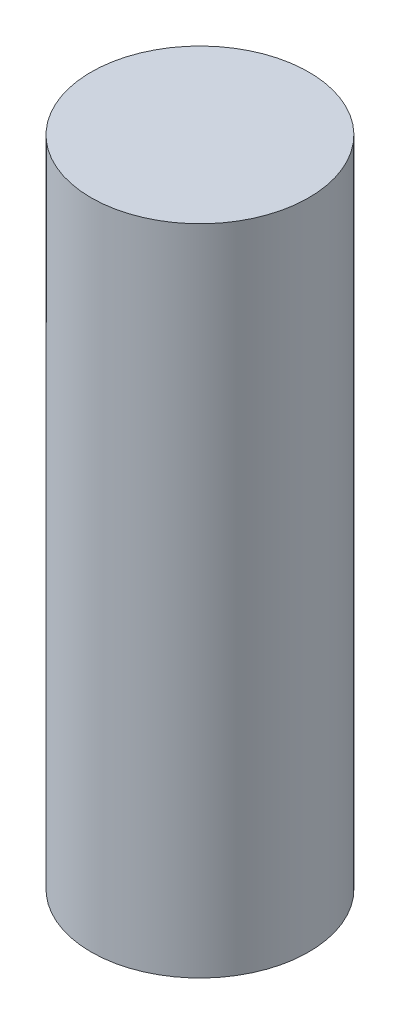
SolidWorks part; units mm, degrees
ref_plane "Front Plane" through (0, 0, 0) normal (0, 0, 1) x (1, 0, 0)
ref_plane "Top Plane" through (0, 0, 0) normal (0, 1, 0) x (1, 0, 0)
ref_plane "Right Plane" through (0, 0, 0) normal (1, 0, 0) x (0, 0, -1)
sketch "Sketch1" plane through (0, 0, 0) normal (0, 1, 0) x (1, 0, 0)
  circle A0 centre (0, 0) radius 5
  dimension "D1" = 10
extrude "Boss-Extrude1" add sketch "Sketch1" along normal blind 30
sketch "Sketch2" plane through (0, 0, 0) normal (0, -1, 0) x (1, 0, 0)
  line L1 (-1.4, -1.4) -> (1.4, -1.4)
  line L2 (-1.4, -1.4) -> (-1.4, 1.4)
  line L3 (-1.4, 1.4) -> (1.4, 1.4)
  line L4 (1.4, -1.4) -> (1.4, 1.4)
  line L5 (-1.4, -1.4) -> (1.4, 1.4) construction
  line L6 (-1.4, 1.4) -> (1.4, -1.4) construction
  point P0 (0, 0)
  dimension "D1" = 2.8
extrude "Cut-Extrude1" cut sketch "Sketch2" against normal blind 3
